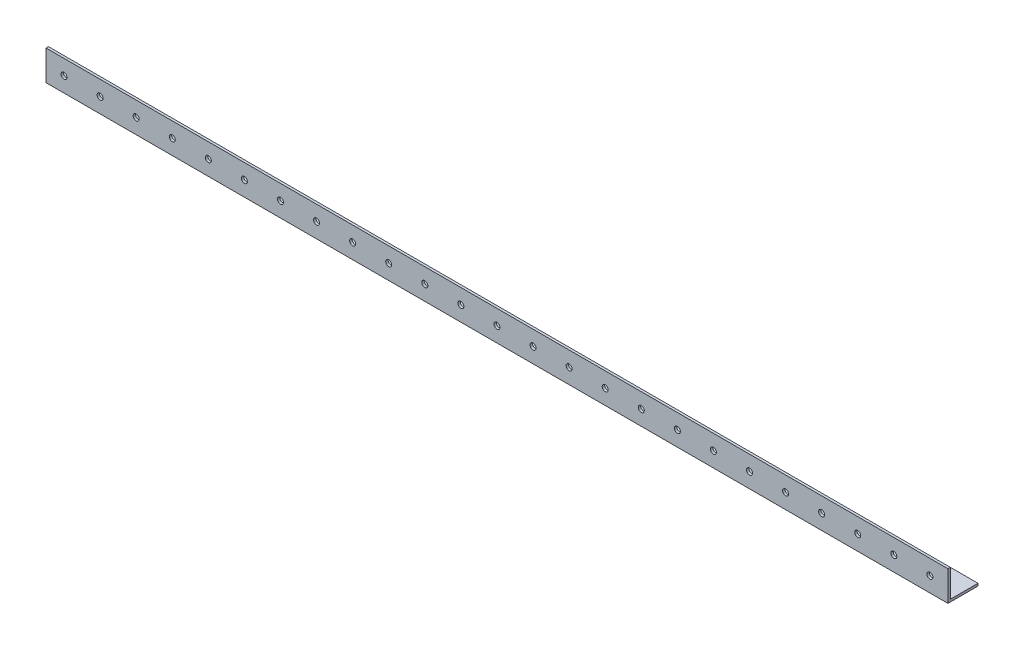
SolidWorks part; units mm, degrees
ref_plane "Спереди" through (0, 0, 0) normal (0, 0, 1) x (1, 0, 0)
ref_plane "Сверху" through (0, 0, 0) normal (0, 1, 0) x (1, 0, 0)
ref_plane "Справа" through (0, 0, 0) normal (1, 0, 0) x (0, 0, -1)
sketch "Эскиз1" plane through (0, 0, 0) normal (1, 0, 0) x (0, 0, -1)
  line L0 (0, 0) -> (0, 50)
  line L1 (0, 0) -> (50, 0)
  dimension "D1" = 50
  dimension "D2" = 50
extrude "Вытянуть-Тонкостенный1" add sketch "Эскиз1" along normal blind 1500 thin thin type one direction reverse wall 4
sketch "Эскиз2" plane through (0, 0, 0) normal (0, 0, 1) x (1, 0, 0)
  circle A0 centre (30, 25) radius 5
  circle A1 centre (90, 25) radius 5
  circle A2 centre (150, 25) radius 5
  circle A3 centre (210, 25) radius 5
  circle A8 centre (270, 25) radius 5
  circle A9 centre (330, 25) radius 5
  circle A10 centre (390, 25) radius 5
  circle A11 centre (450, 25) radius 5
  circle A12 centre (510, 25) radius 5
  circle A13 centre (570, 25) radius 5
  circle A14 centre (630, 25) radius 5
  circle A15 centre (690, 25) radius 5
  circle A16 centre (750, 25) radius 5
  circle A17 centre (810, 25) radius 5
  circle A18 centre (870, 25) radius 5
  circle A19 centre (930, 25) radius 5
  circle A20 centre (990, 25) radius 5
  circle A21 centre (1050, 25) radius 5
  circle A22 centre (1110, 25) radius 5
  circle A23 centre (1170, 25) radius 5
  circle A24 centre (1230, 25) radius 5
  circle A25 centre (1290, 25) radius 5
  circle A26 centre (1350, 25) radius 5
  circle A27 centre (1410, 25) radius 5
  circle A28 centre (1470, 25) radius 5
  dimension "D1" = 25
extrude "Вырез-Вытянуть1" cut sketch "Эскиз2" against normal through all
sketch "Эскиз3" plane through (0, 0, 0) normal (0, -1, 0) x (1, 0, 0)
  circle A0 centre (30, -25) radius 5
  circle A1 centre (90, -25) radius 5
  circle A2 centre (150, -25) radius 5
  circle A3 centre (210, -25) radius 5
  circle A4 centre (270, -25) radius 5
  circle A5 centre (330, -25) radius 5
  circle A6 centre (390, -25) radius 5
  circle A7 centre (450, -25) radius 5
  circle A8 centre (510, -25) radius 5
  circle A9 centre (570, -25) radius 5
  circle A10 centre (630, -25) radius 5
  circle A11 centre (690, -25) radius 5
  circle A12 centre (750, -25) radius 5
  circle A13 centre (810, -25) radius 5
  circle A14 centre (870, -25) radius 5
  circle A15 centre (930, -25) radius 5
  circle A16 centre (990, -25) radius 5
  circle A17 centre (1050, -25) radius 5
  circle A18 centre (1110, -25) radius 5
  circle A19 centre (1170, -25) radius 5
  circle A20 centre (1230, -25) radius 5
  circle A21 centre (1290, -25) radius 5
  circle A22 centre (1350, -25) radius 5
  circle A23 centre (1410, -25) radius 5
  circle A24 centre (1470, -25) radius 5
  dimension "D1" = 25
extrude "Вырез-Вытянуть2" cut sketch "Эскиз3" against normal through all
